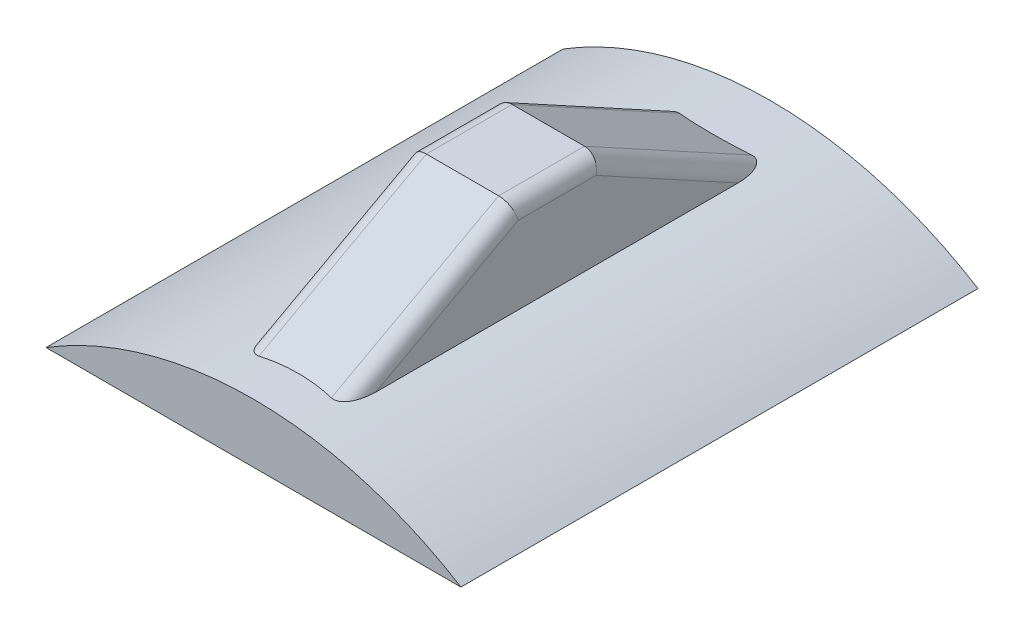
SolidWorks part; units mm, degrees
ref_plane "Front Plane" through (0, 0, 0) normal (0, 0, 1) x (1, 0, 0)
ref_plane "Top Plane" through (0, 0, 0) normal (0, 1, 0) x (1, 0, 0)
ref_plane "Right Plane" through (0, 0, 0) normal (1, 0, 0) x (0, 0, -1)
sketch "Sketch3" plane through (0, 0, 0) normal (0, 0, 1) x (1, 0, 0)
  line L0 (0, 0) -> (0, 8) construction
  line L1 (-10, 8) -> (10, 8)
  line L2 (-10, 8) -> (-10, -10)
  line L4 (10, 8) -> (10, -10)
  arc A0 (-10, -10) -> (10, -10) centre (0, -85.541) cw
  point P0 (0, 0)
  dimension "D3" = 76.2
  dimension "D1" = 20
  dimension "D2" = 18
  dimension "D4" = 8
  dimension "D5" = 18
extrude "Boss-Extrude1" add sketch "Sketch3" along normal blind 82.55
sketch "Sketch4" plane through (-10, 0, 0) normal (-1, 0, 0) x (0, 0, 1)
  line L0 (0, 0) -> (0, -10) construction
  line L1 (0, -10) -> (32.9728, 8)
  line L2 (82.55, 8) -> (0, 8) construction
  line L3 (82.55, -10) -> (0, -10) construction
  line L4 (6.6262, -10) -> (5.1049, -7.2132) construction
  line L5 (6.6262, -10) -> (34.4941, 5.2132) construction
  line L6 (5.1049, -7.2132) -> (32.9728, 8) construction
  line L7 (34.4941, 5.2132) -> (32.9728, 8) construction
  line L8 (0, -10) -> (0, 8)
  line L9 (0, 8) -> (32.9728, 8)
  line L10 (41.275, 8) -> (41.275, -10) construction
  line L11 (82.55, 8) -> (49.5772, 8)
  line L12 (82.55, -10) -> (82.55, 8)
  line L13 (82.55, -10) -> (49.5772, 8)
  dimension "D1" = 3.175
  dimension "D2" = 31.75
extrude "Cut-Extrude1" cut sketch "Sketch4" against normal through all
sketch "Sketch6" plane through (0, -7.7041, 4.2057) normal (0, 0.8777, -0.4792) x (1, 0, 0)
  line L0 (0, 3.4162) -> (0, -32.7745) construction
  line L1 (10, -32.7745) -> (-10, -32.7745) construction
  line L2 (0, -32.7745) -> (6.35, -32.7745) construction
  line L4 (6.35, -32.7745) -> (-6.4117, -32.7745)
  line L5 (6.35, -32.7745) -> (6.35, -1.0245)
  line L6 (6.35, -1.0245) -> (-6.4117, -1.0245)
  line L7 (-6.4117, -32.7745) -> (-6.4117, -1.0245)
  ellipse E0 centre (0, 162.4458) end of major axis (0, 321.4753) minor radius 76.2 (-10, 4.7916) -> (10, 4.7916) ccw construction
  dimension "D1" = 6.35
  dimension "D2" = 31.75
  dimension "D3" = 12.7617
fillet "Fillet3" radius 3 3 edges at (10, -1, 16.4864) (10, 8, 41.275) (10, -1, 66.0636) type face fillet first side face at (10, -1, 41.275) second side face at (0, -0.8352, 16.7882) second side face at (0, 8, 41.275) second side face at (0, -0.8352, 65.7618)
fillet "Fillet4" radius 3 3 edges at (-10, 8, 41.275) (-10, -1, 16.4864) (-10, -1, 66.0636) type face fillet first side face at (-10, -1, 41.275) second side face at (-1.5024, -0.7969, 65.6915) second side face at (-1.5, 8, 41.275) second side face at (-1.5024, -0.7969, 16.8585)
sketch "Sketch7" plane through (0, 8, 0) normal (0, 1, 0) x (1, 0, 0)
  line L0 (-7, -41.275) -> (-5, -41.275) construction
  line L1 (-7, -32.9728) -> (-7, -49.5772) construction
  line L2 (0, -32.9728) -> (0, -49.5772) construction
  line L3 (7, -49.5772) -> (-7, -49.5772) construction
  line L4 (7, -41.275) -> (5, -41.275) construction
  circle A0 centre (-5, -41.275) radius 1
  circle A1 centre (5, -41.275) radius 1
  dimension "D2" = 2
  dimension "D1" = 2
extrude "Cut-Extrude3" cut sketch "Sketch7" against normal blind 2
fillet "Fillet5" radius 0.2 2 edges at (-5, 8, 42.275) (5, 8, 40.275)
extrude "Cut-Extrude4" cut sketch "Sketch6" against normal blind 1.7
sketch "Sketch8" plane through (-10, 0, 0) normal (-1, 0, 0) x (0, 0, 1)
  line L0 (76.289, -10) -> (6.261, -10) construction
  line L1 (41.275, -10) -> (41.275, -8) construction
  line L2 (64.275, -8) -> (18.275, -8) construction
  circle A0 centre (18.275, -8) radius 1
  circle A1 centre (64.275, -8) radius 1
  dimension "D3" = 2
  dimension "D1" = 2
  dimension "D2" = 23
extrude "Cut-Extrude5" cut sketch "Sketch8" against normal blind 2
fillet "Fillet10" radius 0.2 2 edges at (-10, -7, 64.275) (-10, -9, 18.275)
mirror "Mirror3" about plane through (0, 0, 0) normal (1, 0, 0) of "Cut-Extrude5"
fillet "Fillet11" radius 0.2 2 edges at (10, -9, 18.275) (10, -7, 64.275)
shell "Shell10" thickness 1.5 removed face at (9.8, -8, 19.275) removed face at (9.8, -8, 65.275) removed face at (-9.8, -7, 18.275) removed face at (-9.8, -7, 64.275) removed face at (-0.0308, -7.9593, 5.5122) removed face at (6.35, -0.3527, 19.4462) removed face at (-6.4117, -0.3527, 19.4462) removed face at (-5, 7.8, 40.275) removed face at (5, 7.8, 40.275) removed face at (-0.0308, -1.0987, 19.8534) removed face at (0, -9.7482, 41.275) removed face at (-0.0308, 7.2539, 33.3801) removed face at (-8, -7, 64.275) removed face at (-8, -9, 18.275) removed face at (8, -9, 18.275) removed face at (8, -7, 64.275) removed face at (5, 6, 40.275) removed face at (-5, 6, 42.275)
sketch "Sketch9" plane through (0, 0, 0) normal (0, 0, 1) x (1, 0, 0)
  line L0 (-10, -10) -> (10, -10)
  arc A0 (-7, -9.6632) -> (-10, -10) centre (0, -85.541) ccw construction
  arc A1 (10, -10) -> (7, -9.6632) centre (0, -85.541) ccw construction
  arc A2 (7, -9.6632) -> (-7, -9.6632) centre (0, -85.541) ccw construction
  arc A3 (-7, -9.6632) -> (-10, -10) centre (0, -85.541) ccw
  arc A4 (10, -10) -> (7, -9.6632) centre (0, -85.541) ccw
  arc A5 (7, -9.6632) -> (-7, -9.6632) centre (0, -85.541) ccw
  circle A6 centre (0, -85.541) radius 76.2
extrude "Boss-Extrude4" add sketch "Sketch9" along normal blind 90 and the other way blind 10 contours A6
sketch "Sketch10" plane through (6.35, 0, 0) normal (-1, 0, 0) x (0, 0, 1)
  line L6 (5.8236, -8.5298) -> (33.3556, 6.5)
  line L7 (33.3556, 6.5) -> (33.773, 6.5)
  line L8 (33.773, 6.5) -> (33.7874, 6.5079)
  line L9 (33.7874, 6.5079) -> (32.9728, 8)
  line L10 (32.9728, 8) -> (5.1049, -7.2132)
  line L11 (5.1049, -7.2132) -> (5.8236, -8.5298)
  line L12 (5.8236, -8.5298) -> (33.3556, 6.5)
  line L13 (33.3556, 6.5) -> (33.773, 6.5)
  line L14 (33.773, 6.5) -> (33.7874, 6.5079)
  line L15 (33.7874, 6.5079) -> (32.9728, 8)
  line L16 (32.9728, 8) -> (5.1049, -7.2132)
  line L17 (5.1049, -7.2132) -> (5.8236, -8.5298)
  dimension "D1" = 0
extrude "Boss-Extrude5" add sketch "Sketch10" along normal up to vertex (12.7617 mm away) up to point (-6.4117, 8, 32.9728)
sketch "Sketch11" plane through (0, 0, 90) normal (0, 0, 1) x (1, 0, 0)
  line L0 (0, -9.341) -> (0, -85.541) construction
  line L1 (-98.8738, -20.7602) -> (98.8738, -20.7602)
  line L2 (-98.8738, -20.7602) -> (-98.8738, -168.8024)
  line L3 (-98.8738, -168.8024) -> (98.8738, -168.8024)
  line L4 (98.8738, -20.7602) -> (98.8738, -168.8024)
  circle A1 centre (0, -85.541) radius 76.2
  circle A2 centre (0, -85.541) radius 76.2
  point P8 (0, -20.7602)
  circle M7 centre (0, -85.541) radius 76.2
  dimension "D1" = 0
extrude "Cut-Extrude6" cut sketch "Sketch11" against normal through all both and the other way through all contours L1 M7 region at (0, -87.9848, 90)
sketch "Sketch12" plane through (-10, 0, 0) normal (-1, 0, 0) x (0, 0, 1)
  line L4 (6.261, -10) -> (76.289, -10)
  line L5 (76.289, -10) -> (48.8116, 5)
  line L6 (48.8116, 5) -> (33.7384, 5)
  line L7 (33.7384, 5) -> (6.261, -10)
  line L8 (6.261, -10) -> (76.289, -10)
  line L9 (76.289, -10) -> (48.8116, 5)
  line L10 (48.8116, 5) -> (33.7384, 5)
  line L11 (33.7384, 5) -> (6.261, -10)
  dimension "D1" = 0
extrude "Boss-Extrude6" add sketch "Sketch12" against normal up to surface (20 mm away) up to face at (10, -8, 19.475)
sketch "Sketch13" plane through (0, 8, 0) normal (0, 1, 0) x (1, 0, 0)
  line L4 (7, -32.9728) -> (-7, -32.9728)
  line L5 (-7, -32.9728) -> (-7, -49.5772)
  line L6 (-7, -49.5772) -> (7, -49.5772)
  line L7 (7, -49.5772) -> (7, -32.9728)
  line L8 (7, -32.9728) -> (-7, -32.9728)
  line L9 (-7, -32.9728) -> (-7, -49.5772)
  line L10 (-7, -49.5772) -> (7, -49.5772)
  line L11 (7, -49.5772) -> (7, -32.9728)
  dimension "D1" = 0
extrude "Boss-Extrude7" add sketch "Sketch13" against normal up to surface (3 mm away) up to face at (0, 5, 41.275)
